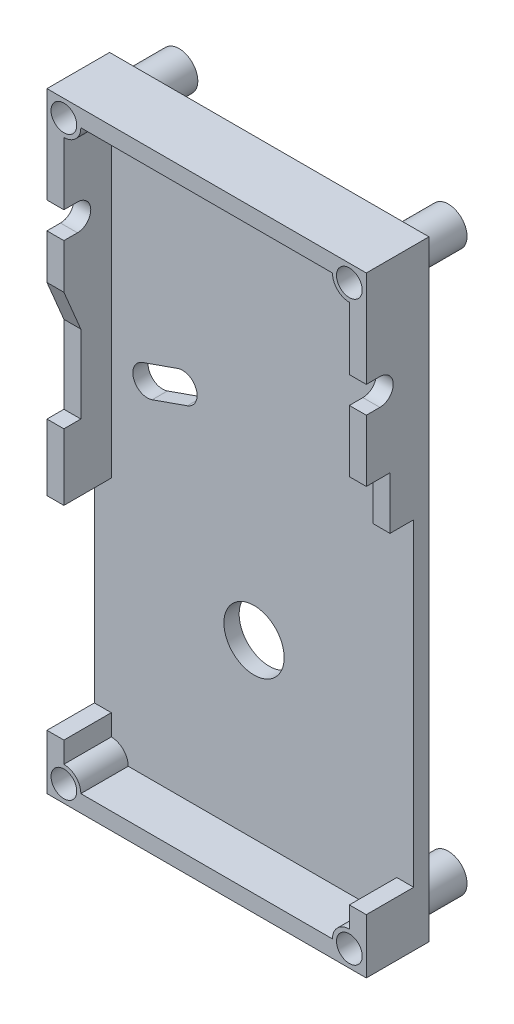
SolidWorks part; units mm, degrees
ref_plane "Front Plane" through (0, 0, 0) normal (0, 0, 1) x (1, 0, 0)
ref_plane "Top Plane" through (0, 0, 0) normal (0, 1, 0) x (1, 0, 0)
ref_plane "Right Plane" through (0, 0, 0) normal (1, 0, 0) x (0, 0, -1)
sketch "Sketch2" plane through (0, 0, 0) normal (0, 0, 1) x (1, 0, 0)
  line L0 (-7.9993, 4.1087) -> (-5.3634, 5.0353) construction
  line L1 (-11.9761, -22.8981) -> (11.9761, -22.8981)
  line L2 (-11.9761, -22.8981) -> (-11.9761, 22.8981)
  line L3 (-11.9761, 22.8981) -> (11.9761, 22.8981)
  line L4 (11.9761, -22.8981) -> (11.9761, 22.8981)
  line L5 (-11.9761, -22.8981) -> (11.9761, 22.8981) construction
  line L6 (-11.9761, 22.8981) -> (11.9761, -22.8981) construction
  line L7 (-8.3615, 5.1391) -> (-5.7256, 6.0657)
  line L8 (-7.6371, 3.0783) -> (-5.0012, 4.0049)
  arc A0 (-8.3615, 5.1391) -> (-7.6371, 3.0783) centre (-7.9993, 4.1087) ccw
  arc A1 (-5.0012, 4.0049) -> (-5.7256, 6.0657) centre (-5.3634, 5.0353) ccw
  circle A2 centre (0, -8.7249) radius 2.2606
  point P0 (0, 0)
  point P8 (-6.6814, 4.572)
  point P13 (-4.333, 5.3975)
  point P14 (-9.0297, 3.7465)
  dimension "D3" = 3.8862
  dimension "D8" = 4.5212
  dimension "D9" = 14.1732
  dimension "D1" = 23.9522
  dimension "D2" = 45.7962
  dimension "D4" = 2.1844
  dimension "D5" = 19.1516
  dimension "D6" = 2.9464
  dimension "D7" = 17.5006
extrude "Boss-Extrude1" add sketch "Sketch2" along normal blind 4.699
sketch "Sketch4" plane through (0, 0, 4.699) normal (0, 0, 1) x (1, 0, 0)
  line L0 (11.9761, -22.8981) -> (11.9761, 22.8981) construction
  line L1 (-10.7061, -21.6281) -> (10.7061, -21.6281)
  line L2 (-10.7061, -21.6281) -> (-10.7061, 21.6281)
  line L3 (-10.7061, 21.6281) -> (10.7061, 21.6281)
  line L4 (10.7061, -21.6281) -> (10.7061, 21.6281)
  line L5 (-10.7061, -21.6281) -> (10.7061, 21.6281) construction
  line L6 (-10.7061, 21.6281) -> (10.7061, -21.6281) construction
  line L7 (11.9761, 22.8981) -> (-11.9761, 22.8981) construction
  point P0 (0, 0)
  dimension "D1" = 1.27
  dimension "D2" = 1.27
extrude "Cut-Extrude1" cut sketch "Sketch4" against normal blind 3.556
sketch "Sketch5" plane through (0, 0, 0) normal (0, 0, -1) x (-1, 0, 0)
  line L0 (-11.9761, 22.8981) -> (11.9761, 22.8981) construction
  line L1 (-11.9761, -22.8981) -> (-11.9761, 22.8981) construction
  line L2 (0, 0) -> (0, 23.8259) construction
  line L3 (0, 0) -> (-13.5113, 0) construction
  circle A0 centre (-10.0965, 21.0185) radius 1.4097
  circle A1 centre (10.0965, 21.0185) radius 1.4097
  circle A2 centre (10.0965, -21.0185) radius 1.4097
  circle A3 centre (-10.0965, -21.0185) radius 1.4097
  dimension "D1" = 2.8194
  dimension "D2" = 1.8796
  dimension "D3" = 1.8796
extrude "Boss-Extrude2" add sketch "Sketch5" along normal blind 3.3274 contours A0 | A3 | A2 | A1
sketch "Sketch6" plane through (-11.9761, 0, 0) normal (-1, 0, 0) x (0, 0, 1)
  line L0 (2.3495, -22.8981) -> (2.3495, -18.7833) construction
  line L1 (4.699, -22.8981) -> (0, -22.8981) construction
  line L2 (4.699, -18.7833) -> (1.143, -18.7833)
  line L3 (4.699, 22.8981) -> (4.699, -22.8981) construction
  line L4 (1.143, -18.7833) -> (1.143, -3.5433)
  line L5 (1.143, -3.5433) -> (4.699, -3.5433)
  line L6 (4.699, -18.7833) -> (4.699, -3.5433)
  line L8 (4.699, 1.4351) -> (3.429, 1.4351)
  line L9 (3.429, 1.4351) -> (3.429, 7.2771)
  line L10 (3.429, 7.2771) -> (4.699, 10.3062)
  line L11 (4.699, 10.3062) -> (4.699, 1.4351)
  line L12 (4.699, 22.8981) -> (0, 22.8981) construction
  line L16 (3.683, 13.659) -> (4.699, 13.659)
  line L17 (4.699, 13.659) -> (4.699, 15.659)
  line L18 (4.699, 15.659) -> (3.683, 15.659)
  arc A0 (3.683, 15.659) -> (3.683, 13.659) centre (3.683, 14.659) ccw
  line M4 (4.699, -22.8981) -> (4.699, 22.8981)
  dimension "D9" = 2
  dimension "D10" = 3.3528
  dimension "D1" = 4.1148
  dimension "D2" = 3.556
  dimension "D3" = 15.24
  dimension "D4" = 1.27
  dimension "D5" = 5.842
  dimension "D6" = 12.5919
  dimension "D7" = 4.9784
  dimension "D8" = 1.016
extrude "Cut-Extrude3" cut sketch "Sketch6" against normal blind 2.54 contours L11 L8 L9 L10 | L6 L5 L4 L2
extrude "Cut-Extrude4" cut sketch "Sketch6<5>" against normal through all contours L18 A0 L16 M4 region at (-11.9761, 14.659, 3.7845)
sketch "Sketch6<5>" plane through (-11.9761, 0, 0) normal (-1, 0, 0) x (0, 0, 1) same geometry as "Sketch6"
sketch "Sketch8" plane through (11.9761, 0, 0) normal (1, 0, 0) x (0, 0, -1)
  line L0 (-2.3495, -22.8981) -> (-2.3495, -18.7833) construction
  line L1 (-4.699, -22.8981) -> (0, -22.8981) construction
  line L2 (-4.699, -18.7833) -> (-1.143, -18.7833)
  line L3 (-4.699, -22.8981) -> (-4.699, 13.659) construction
  line L4 (-1.143, -18.7833) -> (-1.143, 5.0927)
  line L5 (-1.143, 5.0927) -> (-2.921, 5.0927)
  line L6 (-2.921, 5.0927) -> (-2.921, 9.0297)
  line L7 (-2.921, 9.0297) -> (-4.699, 9.0297)
  line L8 (-4.699, 9.0297) -> (-4.699, -18.7833)
  dimension "D1" = 4.1148
  dimension "D2" = 3.556
  dimension "D3" = 23.876
  dimension "D4" = 1.778
  dimension "D5" = 3.937
extrude "Cut-Extrude5" cut sketch "Sketch8" against normal blind 2.54
sketch "Sketch10" plane through (0, 0, 1.143) normal (0, 0, 1) x (1, 0, 0)
  line L0 (10.7061, 21.6281) -> (-10.7061, 21.6281) construction
  line L1 (-10.7061, 21.6281) -> (-10.7061, -3.5433) construction
  line L2 (-10.7061, 20.3581) -> (-10.7061, 21.6281)
  line L3 (-10.7061, 21.6281) -> (-9.4361, 21.6281)
  line L4 (0, 0) -> (0, 25.968) construction
  line L5 (-14.6333, 0) -> (20.9626, 0) construction
  line L6 (10.7061, 20.3581) -> (10.7061, 21.6281)
  line L7 (10.7061, 21.6281) -> (9.4361, 21.6281)
  line L8 (-10.7061, -20.3581) -> (-10.7061, -21.6281)
  line L9 (-10.7061, -21.6281) -> (-9.4361, -21.6281)
  line L10 (10.7061, -21.6281) -> (9.4361, -21.6281)
  line L11 (10.7061, -20.3581) -> (10.7061, -21.6281)
  arc A0 (-9.4361, 21.6281) -> (-10.7061, 20.3581) centre (-10.7061, 21.6281) cw
  circle A2 centre (-10.7061, 21.6281) radius 0.9652
  arc A3 (9.4361, 21.6281) -> (10.7061, 20.3581) centre (10.7061, 21.6281) ccw
  circle A4 centre (10.7061, 21.6281) radius 0.9652
  arc A5 (-9.4361, -21.6281) -> (-10.7061, -20.3581) centre (-10.7061, -21.6281) ccw
  circle A6 centre (-10.7061, -21.6281) radius 0.9652
  arc A7 (9.4361, -21.6281) -> (10.7061, -20.3581) centre (10.7061, -21.6281) cw
  circle A8 centre (10.7061, -21.6281) radius 0.9652
  line M5 (10.7061, 5.0927) -> (10.7061, 21.6281)
  line M6 (10.7061, 21.6281) -> (-10.7061, 21.6281)
  line M7 (-10.7061, 21.6281) -> (-10.7061, -3.5433)
  line M11 (-10.7061, -18.7833) -> (-10.7061, -21.6281)
  line M12 (-10.7061, -21.6281) -> (10.7061, -21.6281)
  dimension "D1" = 1.27
  dimension "D2" = 1.9304
extrude "Boss-Extrude3" add sketch "Sketch10" along normal up to surface (3.556 mm away) contours A0 M6 M7 | A4 L7 A3 M5 | A8 L11 A7 M12 | A6 L9 A5 M11 region at (9.9902, 20.9122, 1.143) region at (-9.9902, 20.9122, 1.143) region at (-9.9902, -20.9122, 1.143) region at (9.9902, -20.9122, 1.143) up to face at (0, 18.961, 4.699)
sketch "Sketch12" plane through (0, 0, 4.699) normal (0, 0, 1) x (1, 0, 0)
  line L0 (0, 0) -> (0, 30.6011) construction
  line L1 (-17.4939, 0) -> (16.8903, 0) construction
  circle A0 centre (-10.7061, 21.6281) radius 0.9652
  circle A1 centre (10.7061, 21.6281) radius 0.9652
  circle A2 centre (10.7061, -21.6281) radius 0.9652
  circle A3 centre (-10.7061, -21.6281) radius 0.9652
  dimension "D1" = 1.9304
extrude "Cut-Extrude6" cut sketch "Sketch12" against normal blind 3.81
